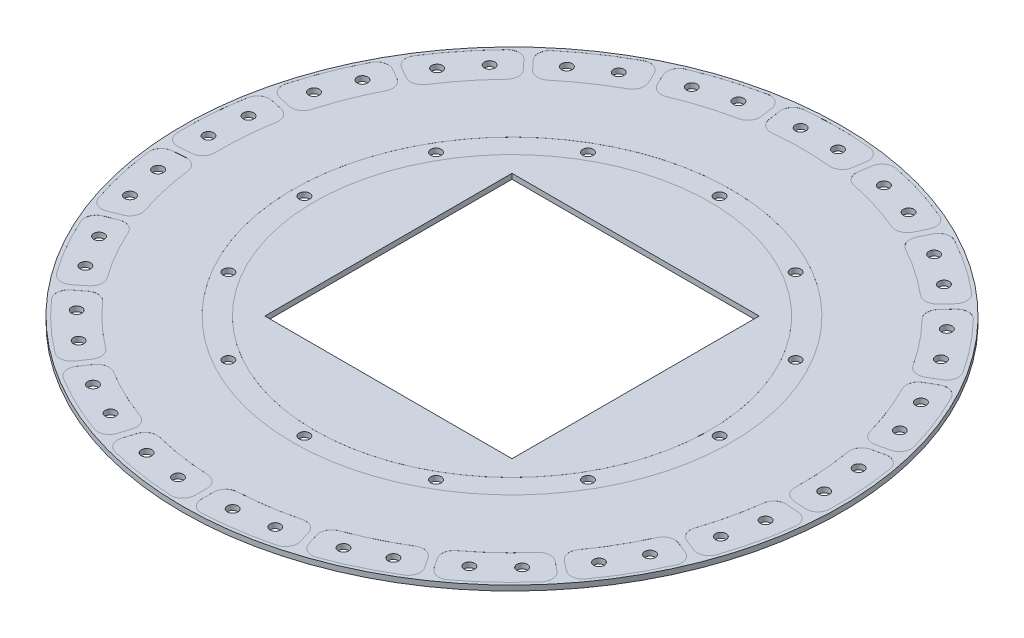
SolidWorks part; units mm, degrees
material "Thornel VCB-20 Carbon Cloth"
ref_plane "Front Plane" through (0, 0, 0) normal (0, 0, 1) x (1, 0, 0)
ref_plane "Top Plane" through (0, 0, 0) normal (0, 1, 0) x (1, 0, 0)
ref_plane "Right Plane" through (0, 0, 0) normal (1, 0, 0) x (0, 0, -1)
sketch "Sketch1" plane through (0, 0, 0) normal (0, 0, 1) x (1, 0, 0)
  line L0 (-60, -0.785) -> (-100, -0.785) construction
  line L1 (-60, 0.785) -> (-60, -0.785) construction
  line L2 (-60, 0.785) -> (-100, 0.785) construction
  line L3 (-100, 0.785) -> (-100, -0.785) construction
  line L4 (-60, -0.785) -> (-100, -0.785)
  line L5 (-60, 0.785) -> (-60, -0.785)
  line L6 (-60, 0.785) -> (-100, 0.785)
  line L7 (-100, 0.785) -> (-100, -0.785)
  line L8 (0, -200069.0475) -> (0, 200086.9028) construction
  line L9 (0, -200069.0475) -> (0, 200086.9028) construction
revolve "Revolve1" add sketch "Sketch1" angle 360 about L9
sketch "Sketch2" plane through (0, 0.785, 0) normal (0, 1, 0) x (1, 0, 0)
  line L1 (-37.5, -37.5) -> (37.5, -37.5)
  line L2 (-37.5, -37.5) -> (-37.5, 37.5)
  line L3 (-37.5, 37.5) -> (37.5, 37.5)
  line L4 (37.5, -37.5) -> (37.5, 37.5)
  line L5 (-37.5, -37.5) -> (37.5, 37.5) construction
  line L6 (-37.5, 37.5) -> (37.5, -37.5) construction
  circle A0 centre (0, 0) radius 60 construction
  circle A1 centre (0, 0) radius 60
  dimension "D1" = 75
  dimension "D2" = 75
extrude "Boss-Extrude1" add sketch "Sketch2" against normal up to surface (1.57 mm away) up to face at (0, -0.785, -60)
sketch "Sketch3" plane through (0, 0.785, 0) normal (0, 1, 0) x (1, 0, 0)
  circle A1 centre (0, 63) radius 1.6
  circle A2 centre (0, 63) radius 1.6
  dimension "D1" = 0
extrude "Cut-Extrude1" cut sketch "Sketch3" against normal through all
pattern_circular "CirPattern1" count 12 over 360 about axis through (0, -200069.0475, 0) along (0, -1, 0) of "Cut-Extrude1" reverse direction yes
sketch "Sketch4" plane through (0, 0.785, 0) normal (0, 1, 0) x (1, 0, 0)
  line L0 (13.2089, 94.3447) -> (12.6502, 90.638)
  line L1 (13.2089, 94.3447) -> (12.6502, 90.638)
  line L2 (-12.6502, 90.638) -> (-13.2089, 94.3447)
  line L3 (-12.6502, 90.638) -> (-13.2089, 94.3447)
  arc A0 (0, 99) -> (-9.9874, 98.4949) centre (0, 0) ccw
  arc A1 (0, 99) -> (-9.9874, 98.4949) centre (0, 0) ccw
  arc A2 (9.9874, 98.4949) -> (0, 99) centre (0, 0) ccw
  arc A3 (9.9874, 98.4949) -> (0, 99) centre (0, 0) ccw
  arc A4 (13.2089, 94.3447) -> (9.9874, 98.4949) centre (9.6214, 94.8854) ccw
  arc A5 (13.2089, 94.3447) -> (9.9874, 98.4949) centre (9.6214, 94.8854) ccw
  arc A6 (8.7039, 87.5685) -> (12.6502, 90.638) centre (9.0627, 91.1787) ccw
  arc A7 (8.7039, 87.5685) -> (12.6502, 90.638) centre (9.0627, 91.1787) ccw
  arc A8 (8.7039, 87.5685) -> (-8.7039, 87.5685) centre (0, 0) ccw
  arc A9 (8.7039, 87.5685) -> (-8.7039, 87.5685) centre (0, 0) ccw
  arc A10 (-12.6502, 90.638) -> (-8.7039, 87.5685) centre (-9.0627, 91.1787) ccw
  arc A11 (-12.6502, 90.638) -> (-8.7039, 87.5685) centre (-9.0627, 91.1787) ccw
  arc A12 (-9.9874, 98.4949) -> (-13.2089, 94.3447) centre (-9.6214, 94.8854) ccw
  arc A13 (-9.9874, 98.4949) -> (-13.2089, 94.3447) centre (-9.6214, 94.8854) ccw
extrude "Cut-Extrude2" cut sketch "Sketch4" against normal blind 0.01
sketch "Sketch5" plane through (0, 0.775, 0) normal (0, 1, 0) x (1, 0, 0)
  circle A0 centre (5.6703, 93.2501) radius 1.6 construction
  circle A1 centre (-5.6703, 93.2501) radius 1.6 construction
  circle A2 centre (5.6703, 93.2501) radius 1.6
  circle A3 centre (-5.6703, 93.2501) radius 1.6
extrude "Cut-Extrude3" cut sketch "Sketch5" against normal through all
pattern_circular "CirPattern2" count 21 over 360 about axis through (0, 0.785, 0) along (0, -1, 0) of "Cut-Extrude2", "Cut-Extrude3"
sketch "Sketch6" plane through (0, 0.785, 0) normal (0, 1, 0) x (1, 0, 0)
  circle A0 centre (0, 0) radius 66.5 construction
  circle A1 centre (0, 0) radius 66.5
  circle A2 centre (0, 0) radius 60 construction
  circle A3 centre (0, 0) radius 60
extrude "Cut-Extrude4" cut sketch "Sketch6" against normal blind 0.01
